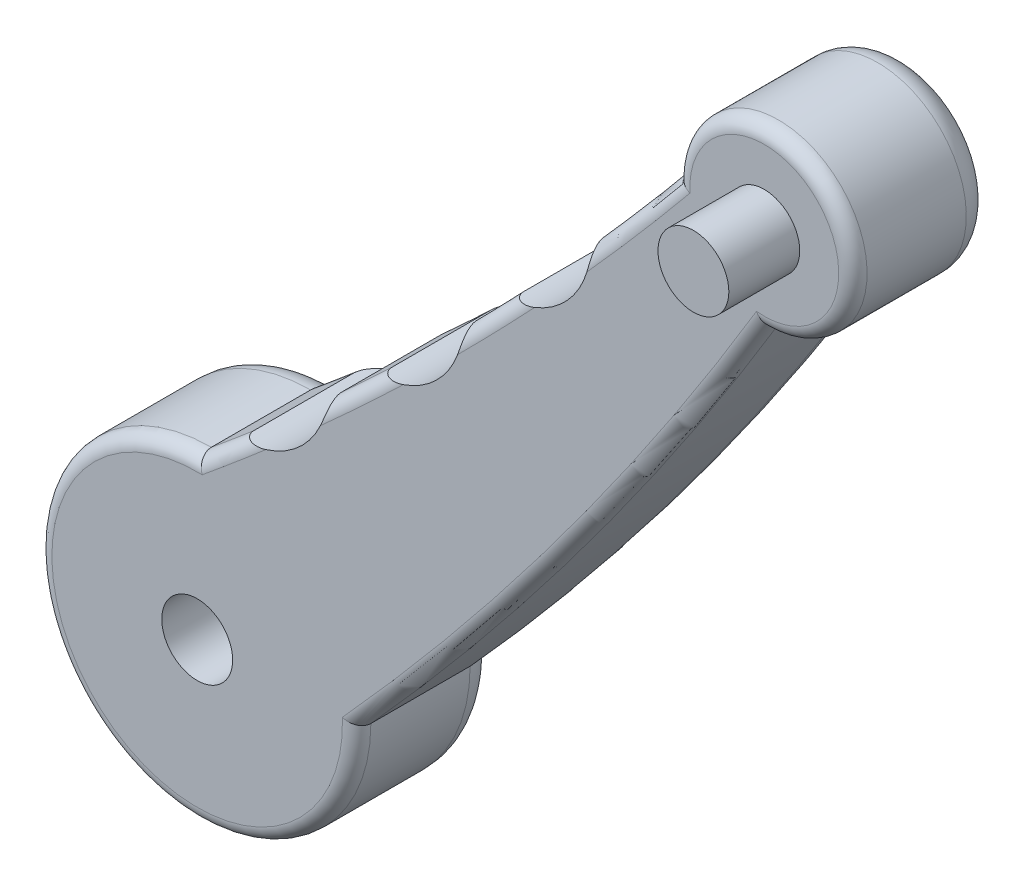
SolidWorks part; units mm, degrees
ref_plane "Front Plane" through (0, 0, 0) normal (0, 0, 1) x (1, 0, 0)
ref_plane "Top Plane" through (0, 0, 0) normal (0, 1, 0) x (1, 0, 0)
ref_plane "Right Plane" through (0, 0, 0) normal (1, 0, 0) x (0, 0, -1)
sketch "Sketch1" plane through (0, 0, 0) normal (0, 0, 1) x (1, 0, 0)
  arc A0 (0, 22.5) -> (22.5, 0) centre (0, 0) ccw
  arc A1 (80, 77.5) -> (67.5, 90) centre (80, 90) ccw
  arc A2 (0, 22.5) -> (67.5, 90) centre (-318.1888, 408.1888) ccw
  arc A3 (22.5, 0) -> (80, 77.5) centre (-348.4249, 335.283) ccw
  dimension "D1" = 45
  dimension "D2" = 25
  dimension "D5" = 500
  dimension "D6" = 500
  dimension "D3" = 80
  dimension "D4" = 90
extrude "Boss-Extrude1" add sketch "Sketch1" along normal mid plane 20
fillet "Fillet1" radius 2 4 edges at (53.1241, 37.3595, 10) (88.8388, 98.8388, 10) (-15.9099, -15.9099, 10) (35.3646, 54.6354, 10)
sketch "Sketch2" plane through (0, 0, 10) normal (0, 0, 1) x (1, 0, 0)
  circle A0 centre (0, 0) radius 5
  circle A1 centre (80, 90) radius 5
  dimension "D1" = 10
  dimension "D2" = 10
extrude "Boss-Extrude2" add sketch "Sketch2" along normal blind 10 contours A1
extrude "Cut-Extrude1" cut sketch "Sketch2<3>" against normal blind 10 contours A0
sketch "Sketch2<3>" plane through (0, 0, 10) normal (0, 0, 1) x (1, 0, 0) same geometry as "Sketch2"
fillet "Fillet2" radius 4 4 edges at (-15.9099, -15.9099, -10) (35.3646, 54.6354, -10) (53.1241, 37.3595, -10) (88.8388, 98.8388, -10)
sketch "Sketch3" plane through (0, 0, -10) normal (0, 0, -1) x (-1, 0, 0)
  circle A0 centre (0, 0) radius 12.5
  dimension "D1" = 25
extrude "Boss-Extrude3" add sketch "Sketch3" along normal blind 5
fillet "Fillet3" radius 5 1 edges at (-12.5, 0, -15)
sketch "Sketch4" plane through (0, 0, -15) normal (0, 0, -1) x (-1, 0, 0)
  line L0 (0, 0) -> (0, 12.5) construction
  circle A0 centre (0, 0) radius 12.5 construction
  circle A1 centre (0, 12.5) radius 2.5
  dimension "D2" = 5
  dimension "D1" = 12.5
extrude "Cut-Extrude2" cut sketch "Sketch4" against normal up to surface (5 mm away) up to face at (12.5, 0, -10)
pattern_circular "CirPattern1" count 8 over 360 about axis through (0, 0, -15) along (0, 0, -1) of "Cut-Extrude2"
sketch "Sketch5" plane through (0, 0, -10) normal (0, 0, -1) x (-1, 0, 0)
  circle A0 centre (8.8388, 8.8388) radius 1.75
  dimension "D1" = 3.5
extrude "Boss-Extrude5" add sketch "Sketch5" along normal blind 2 contours A0
fillet "Fillet5" radius 1 1 edges at (-10.5888, 8.8388, -12)
pattern_circular "CirPattern5" count 8 over 360 about axis through (0, 0, -15) along (0, 0, -1) of "Fillet5", "Boss-Extrude5"
sketch "Sketch6" plane through (0, 0, -10) normal (0, 0, -1) x (-1, 0, 0)
  circle A0 centre (-80, 90) radius 5
  arc A10 (-73.9217, 86.7883) -> (-3.2738, 16.1292) centre (318.1888, 408.1888) ccw
  arc A11 (-56.9582, 67.1409) -> (-14.497, 25.6066) centre (318.1888, 408.1888) ccw
  arc A12 (-56.9582, 67.1409) -> (-62.465, 62.8524) centre (-59.548, 64.7865) ccw
  arc A13 (-75.3122, 83.2992) -> (-16.2219, 3.4974) centre (348.4249, 335.283) ccw
  arc A14 (-62.465, 62.8524) -> (-25.8194, 14.3622) centre (348.4249, 335.283) ccw
  arc A15 (-25.8194, 14.3622) -> (-14.497, 25.6066) centre (-19.7465, 19.5698) ccw
  dimension "D1" = 3
  dimension "D3" = 7
  dimension "D4" = 16
  dimension "D5" = 10
  dimension "D2" = 3
extrude "Cut-Extrude3" cut sketch "Sketch6" against normal blind 2
sketch "Sketch7" plane through (0, 0, 10) normal (0, 0, 1) x (1, 0, 0)
  circle A0 centre (6, 40) radius 12.5
  circle A1 centre (25, 57.5) radius 12.5
  circle A2 centre (43, 76) radius 12.5
  point P6 (9.5588, 40)
  point P10 (82.5284, 26.9931)
  dimension "D1" = 25
  dimension "D2" = 40
  dimension "D3" = 6
  dimension "D4" = 57.5
  dimension "D5" = 25
  dimension "D6" = 76
  dimension "D7" = 43
extrude "Cut-Extrude4" cut sketch "Sketch7" against normal through all both and the other way through all
